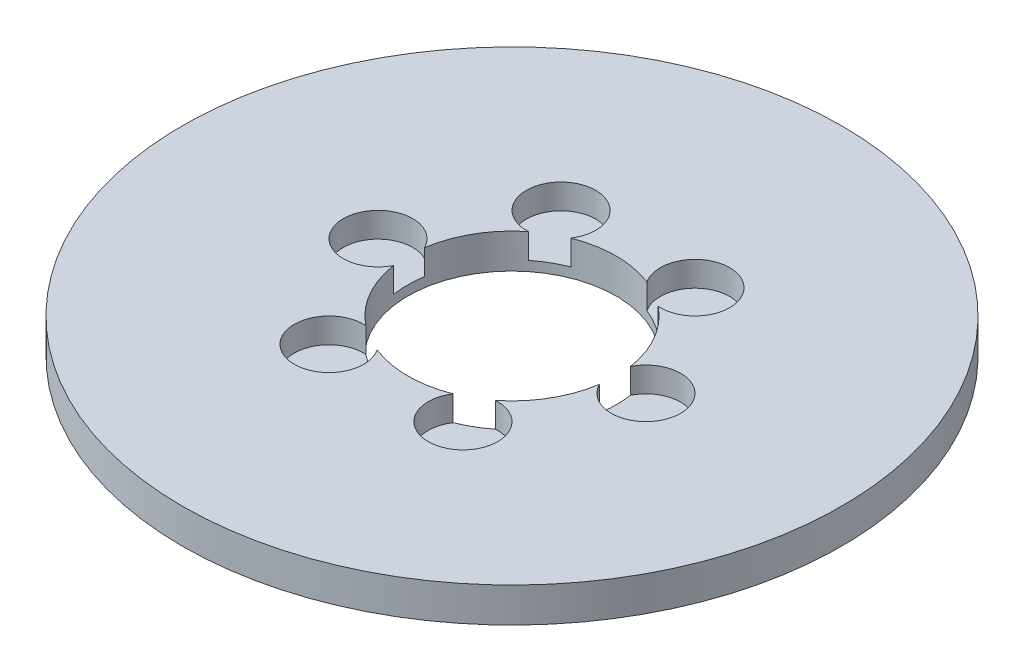
SolidWorks part; units mm, degrees
ref_plane "Front Plane" through (0, 0, 0) normal (0, 0, 1) x (1, 0, 0)
ref_plane "Top Plane" through (0, 0, 0) normal (0, 1, 0) x (1, 0, 0)
ref_plane "Right Plane" through (0, 0, 0) normal (1, 0, 0) x (0, 0, -1)
sketch "Sketch1" plane through (0, 0, 0) normal (0, 1, 0) x (1, 0, 0)
  circle A0 centre (0, 0) radius 95
  dimension "FLANGE_OD" = 190
extrude "Boss-Extrude1" add sketch "Sketch1" along normal blind 10
sketch "Sketch2" plane through (0, 0, 0) normal (0, 1, 0) x (1, 0, 0)
  circle A0 centre (0, 0) radius 30
  dimension "BORE_D" = 60
extrude "Cut-Extrude1" cut sketch "Sketch2" along normal through all
sketch "Sketch3" plane through (0, 10, 0) normal (0, 1, 0) x (1, 0, 0)
  circle A0 centre (0, 0) radius 38.617 construction
  circle A1 centre (-38.617, 0) radius 10
  dimension "BOLT_D" = 20
  dimension "BOLT_PCD" = 77.2341
extrude "Cut-Extrude2" cut sketch "Sketch3" against normal blind 7.1957
pattern_circular "CirPattern1" count 6 over 360 about axis through (0, 0, 0) along (0, 1, 0) of "Cut-Extrude2"
